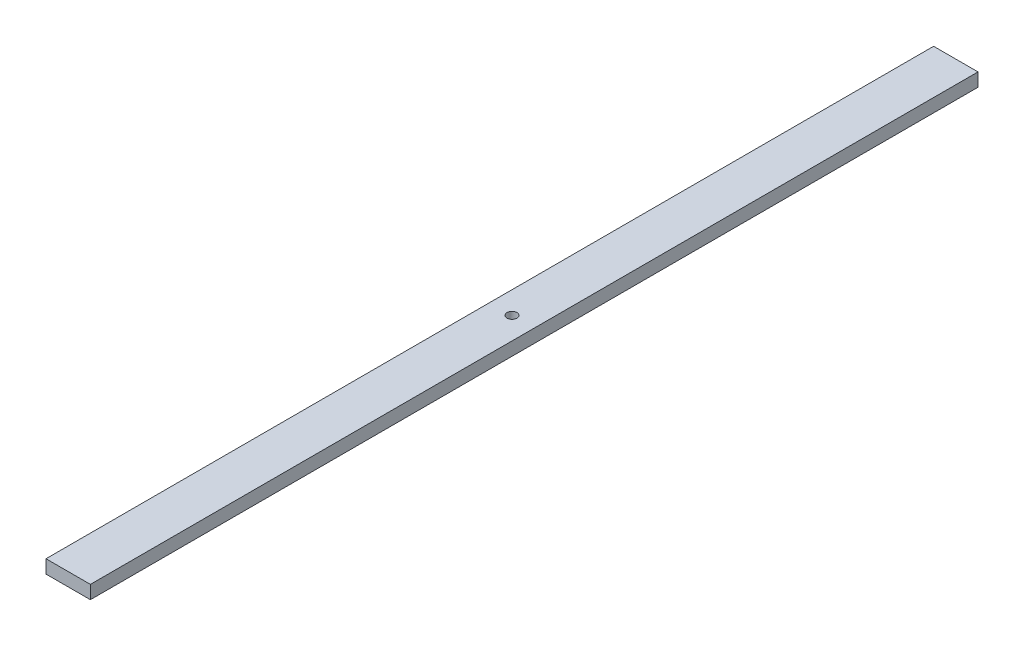
SolidWorks part; units mm, degrees
ref_plane "Front" through (0, 0, 0) normal (0, 0, 1) x (1, 0, 0)
ref_plane "Top" through (0, 0, 0) normal (0, 1, 0) x (1, 0, 0)
ref_plane "Right" through (0, 0, 0) normal (1, 0, 0) x (0, 0, -1)
sketch "Esquisse1" plane through (0, 0, 0) normal (0, 0, 1) x (1, 0, 0)
  line L1 (0, 0) -> (90, 0)
  line L2 (0, 0) -> (0, 27)
  line L3 (0, 27) -> (90, 27)
  line L4 (90, 0) -> (90, 27)
  dimension "D1" = 90
  dimension "D2" = 27
extrude "Boss.-Extru.1" add sketch "Esquisse1" along normal blind 1800
sketch "Esquisse2" plane through (0, 0, 0) normal (0, -1, 0) x (1, 0, 0)
  line L0 (45, 0) -> (45, 1800) construction
  line L1 (0, 0) -> (90, 0) construction
  line L2 (0, 1800) -> (90, 1800) construction
  circle A0 centre (45, 900) radius 10
  dimension "D1" = 20
extrude "Enlèv. mat.-Extru.1" cut sketch "Esquisse2" against normal through all
